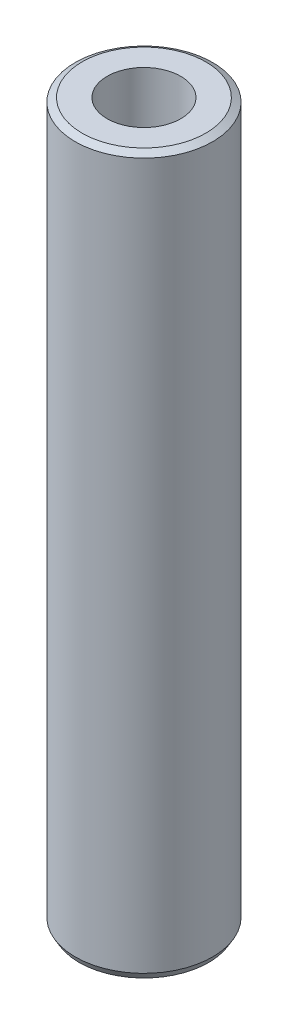
SolidWorks part; units mm, degrees
ref_plane "Front Plane" through (0, 0, 0) normal (0, 0, 1) x (1, 0, 0)
ref_plane "Top Plane" through (0, 0, 0) normal (0, 1, 0) x (1, 0, 0)
ref_plane "Right Plane" through (0, 0, 0) normal (1, 0, 0) x (0, 0, -1)
sketch "Sketch1" plane through (0, 0, 0) normal (0, 1, 0) x (1, 0, 0)
  circle A0 centre (0, 0) radius 57.5
  dimension "SHAFT_OD" = 115
extrude "Boss-Extrude1" add sketch "Sketch1" along normal blind 600
sketch "Sketch2" plane through (0, 0, 0) normal (0, 1, 0) x (1, 0, 0)
  circle A0 centre (0, 0) radius 30.8139
  dimension "BORE_D" = 61.6279
extrude "Cut-Extrude1" cut sketch "Sketch2" along normal through all
chamfer "Chamfer1" distance 3.3082 angle 60 2 edges at (0, 600, 57.5) (0, 0, 57.5) first distance on face at (0, 600, 57.5) first distance on face at (0, 0, 30.8139)
